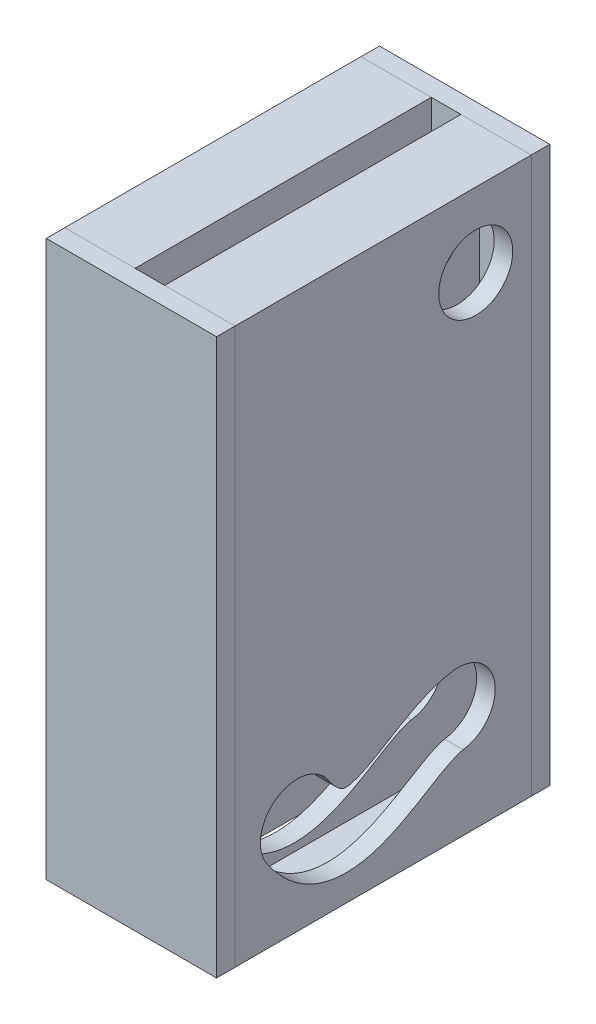
SolidWorks part; units mm, degrees
ref_plane "Front Plane" through (0, 0, 0) normal (0, 0, 1) x (1, 0, 0)
ref_plane "Top Plane" through (0, 0, 0) normal (0, 1, 0) x (1, 0, 0)
ref_plane "Right Plane" through (0, 0, 0) normal (1, 0, 0) x (0, 0, -1)
sketch "Sketch1" plane through (0, 0, 0) normal (0, 0, 1) x (1, 0, 0)
  line L0 (-4, 75) -> (-4, 35)
  line L8 (-4, -35) -> (-4, -75)
  line L9 (-4, -75) -> (-23, -75)
  line L10 (-23, -75) -> (-23, 75)
  line L11 (-23, 75) -> (-4, 75)
  line L12 (0, 171.0434) -> (0, -171.0434) construction
  line L13 (-4, 35) -> (4, 35)
  line L14 (-4, -35) -> (4, -35)
  line L15 (4, -35) -> (4, -75)
  line L16 (4, -75) -> (23, -75)
  line L17 (23, -75) -> (23, 75)
  line L18 (4, 75) -> (4, 35)
  line L19 (23, 75) -> (4, 75)
  line L20 (-18, 70) -> (-9, 70)
  line L21 (-9, 70) -> (-9, 30)
  line L22 (-9, 30) -> (9, 30)
  line L23 (9, 70) -> (9, 30)
  line L24 (18, 70) -> (9, 70)
  line L25 (18, -70) -> (18, 70)
  line L26 (9, -70) -> (18, -70)
  line L27 (9, -30) -> (9, -70)
  line L28 (-9, -30) -> (9, -30)
  line L29 (-9, -30) -> (-9, -70)
  line L30 (-9, -70) -> (-18, -70)
  line L31 (-18, -70) -> (-18, 70)
  line L32 (-71.2515, 55) -> (71.2515, 55) construction
  line L33 (-18, 0) -> (18, 0) construction
  line L34 (-23, 65) -> (23, 65) construction
  line L35 (-23, -65) -> (23, -65) construction
  line L36 (-71.2515, -55) -> (71.2515, -55) construction
  point P6 (0, -35)
  point P16 (0, 35)
  point P31 (0, 0)
  point P34 (0, 55)
  point P35 (-4, 55)
  dimension "D2" = 10
  dimension "D3" = 8
  dimension "D4" = 46
  dimension "D5" = 150
  dimension "D6" = 20
  dimension "D1" = 5
sketch "Sketch2" plane through (0, 0, 0) normal (1, 0, 0) x (0, 0, -1)
  line L0 (-40, 0) -> (40, 0) construction
  line L1 (-40, 0) -> (-45, 0) construction
  line L2 (40, 0) -> (45, 0) construction
  point P4 (0, 0)
  dimension "D1" = 80
  dimension "D2" = 5
extrude "Boss-Extrude1" add sketch "Sketch1" along normal up to vertex (40 mm away) and the other way up to vertex (40 mm away) up to point (0, 0, 40) other way up to point (0, 0, -40)
sketch "Sketch3" plane through (0, 0, 0) normal (0, 0, 1) x (1, 0, 0)
  line L1 (-23, -75) -> (23, -75)
  line L2 (-23, -75) -> (-23, 75)
  line L3 (-23, 75) -> (23, 75)
  line L4 (23, -75) -> (23, 75)
  line L5 (-23, -75) -> (23, 75) construction
  line L6 (-23, 75) -> (23, -75) construction
  point P0 (0, 0)
extrude "Boss-Extrude2" add sketch "Sketch3" along normal up to vertex (45 mm away) from vertex separate body up to point (0, 0, 45) starting at point (0, 0, 40)
extrude "Boss-Extrude3" add sketch "Sketch3<2>" against normal up to vertex (45 mm away) from vertex separate body up to point (0, 0, -45) starting at point (0, 0, -40)
sketch "Sketch3<2>" plane through (0, 0, 0) normal (0, 0, 1) x (1, 0, 0) same geometry as "Sketch3"
sketch "Sketch4" plane through (0, 0, 0) normal (1, 0, 0) x (0, 0, -1)
  line L0 (0, 171.0434) -> (0, -171.0434) construction
  line L1 (0, 0) -> (0, 55) construction
  line L2 (0, 55) -> (25, 55) construction
  circle A1 centre (0, -55) radius 10 construction
  arc A2 (-31.4617, -54.9352) -> (-14.8827, -43.7487) centre (-23.1722, -49.342) cw
  arc A3 (21.5877, -54.9129) -> (18.9531, -35.0871) centre (20.2704, -45) ccw
  circle A4 centre (25, 55) radius 10
  spline S0 degree 3 poles (-23.1722, -49.342) (-9.1837, -70.0737) (6.7542, -46.7961) (20.2704, -45) knots 0 0 0 0 1 1 1 1 construction
  spline S1 degree 1 poles (-31.4617, -54.9352) (21.5877, -54.9129) knots 0 0 1 1 construction
  spline S2 degree 3 poles (-31.4617, -54.9352) (-30.913, -55.7484) (-29.7473, -57.359) (-27.3068, -60.2469) (-23.9206, -63.3578) (-19.2822, -66.1168) (-14.2588, -67.686) (-9.2968, -68.0371) (-4.7395, -67.4454) (-0.6629, -66.254) (4.2173, -64.2022) (8.4538, -61.802) (12.2348, -59.5117) (14.8357, -57.9446) (17.1724, -56.627) (18.8426, -55.8121) (19.9554, -55.359) (20.6614, -55.1187) (21.1238, -54.997) (21.4202, -54.9377) (21.5283, -54.9208) (21.5877, -54.9129) knots 0 0 0 0 0.03125 0.0625 0.125 0.1875 0.25 0.3125 0.375 0.4375 0.5 0.625 0.6875 0.75 0.8125 0.875 0.90625 0.9375 0.96875 0.984375 1 1 1 1
  spline S3 degree 1 poles (-14.8827, -43.7487) (18.9531, -35.0871) knots 0 0 1 1 construction
  spline S4 degree 3 poles (-14.8827, -43.7487) (-14.732, -43.9721) (-14.4132, -44.428) (-13.827, -45.2053) (-13.1419, -46.0112) (-12.4318, -46.7144) (-11.6443, -47.3576) (-10.9805, -47.7182) (-10.5151, -47.8548) (-9.948, -47.9126) (-8.6179, -47.7812) (-5.7019, -46.7954) (-0.9385, -44.1508) (3.653, -41.2952) (7.7222, -38.9894) (11.0302, -37.353) (14.0932, -36.1732) (16.7705, -35.4494) (18.2306, -35.1832) (18.9531, -35.0871) knots 0 0 0 0 0.015625 0.03125 0.0625 0.09375 0.125 0.1875 0.25 0.3125 0.375 0.5 0.625 0.75 0.8125 0.875 0.9375 0.96875 1 1 1 1
  point P1 (0, 55)
  point P10 (0, -55)
  dimension "D2" = 10
  dimension "D4" = 25
  dimension "D5" = 20
  dimension "D3" = 10
extrude "Cut-Extrude1" cut sketch "Sketch4" against normal through all and the other way through all
